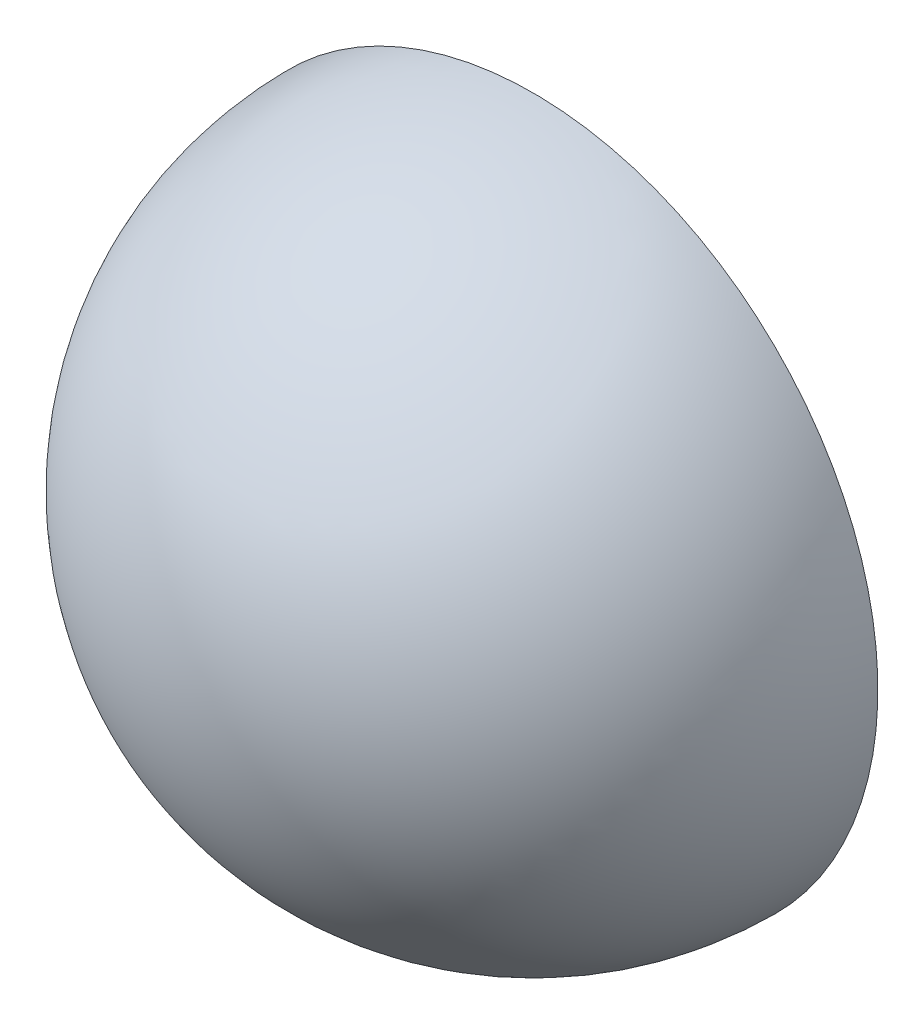
SolidWorks part; units mm, degrees
material "Настроенная пользователем пластмасса"
ref_plane "Спереди" through (0, 0, 0) normal (0, 0, 1) x (1, 0, 0)
ref_plane "Сверху" through (0, 0, 0) normal (0, 1, 0) x (1, 0, 0)
ref_plane "Справа" through (0, 0, 0) normal (1, 0, 0) x (0, 0, -1)
sketch "Эскиз1" plane through (0, 0, 0) normal (0, 1, 0) x (1, 0, 0)
  line L0 (0, 0) -> (0, -2)
  line L1 (0, 0) -> (-2, 0)
  line L2 (0, 0) -> (0, -5.1258) construction
  arc A0 (0, -2) -> (-2, 0) centre (0, 0) cw
  dimension "D1" = 4
revolve "Повернуть1" add sketch "Эскиз1" angle 360 about L2
